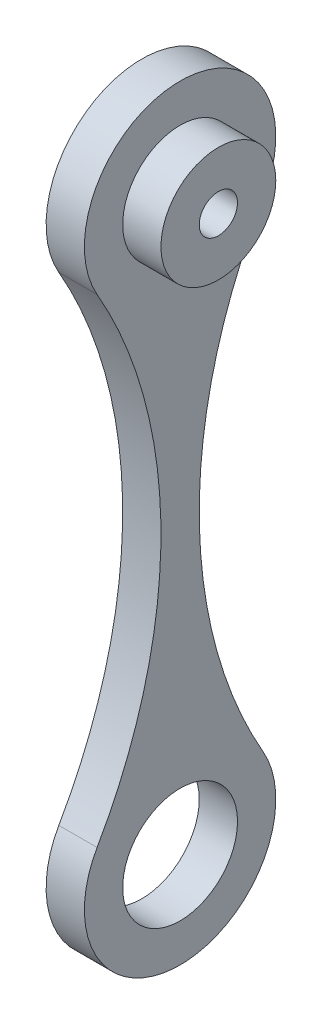
SolidWorks part; units mm, degrees
ref_plane "Front Plane" through (0, 0, 0) normal (0, 0, 1) x (1, 0, 0)
ref_plane "Top Plane" through (0, 0, 0) normal (0, 1, 0) x (1, 0, 0)
ref_plane "Right Plane" through (0, 0, 0) normal (1, 0, 0) x (0, 0, -1)
sketch "Sketch1" plane through (0, 0, 0) normal (1, 0, 0) x (0, 0, -1)
  line L0 (0, 0) -> (0, -150) construction
  circle A0 centre (0, 0) radius 25
  circle A1 centre (0, -150) radius 25
  circle A2 centre (0, 0) radius 15
  circle A3 centre (0, -150) radius 15
  arc A4 (-21.6805, -12.4481) -> (-21.6805, -137.5519) centre (-130.625, -75) cw
  arc A5 (21.6805, -12.4481) -> (21.6805, -137.5519) centre (130.625, -75) ccw
  point P15 (-5, -75)
  point P16 (5, -75)
  dimension "D1" = 50
  dimension "D2" = 50
  dimension "D5" = 10
  dimension "D6" = 10
  dimension "D3" = 150
  dimension "D4" = 10
extrude "Boss-Extrude1" add sketch "Sketch1" along normal blind 10 contours A2 A0 | L0 A0 A4 A1 | A0 L0 A1 A5 | A1 A3 | A2 region at (0, -21.0237, 12.1716) region at (0, -22.7345, -13.1621) region at (0, -75, 1.2697) region at (0, -128.9763, -12.1716)
sketch "Sketch2" plane through (10, 0, 0) normal (1, 0, 0) x (0, 0, -1)
  circle A0 centre (0, 0) radius 15
  arc A1 (21.6805, -12.4481) -> (-21.6805, -12.4481) centre (0, 0) ccw construction
  dimension "D1" = 10
extrude "Boss-Extrude2" add sketch "Sketch2" along normal blind 10
sketch "Sketch3" plane through (20, 0, 0) normal (1, 0, 0) x (0, 0, -1)
  circle A2 centre (0, 0) radius 5
  circle A3 centre (0, 0) radius 5
  dimension "D1" = 10
extrude "Cut-Extrude1" cut sketch "Sketch3" against normal blind 45
ref_plane "Plane1" through (15, 0, 0) normal (1, 0, 0) x (0, 0, -1)
ref_plane "Plane2" through (5, 0, 0) normal (1, 0, 0) x (0, 0, -1)
ref_axis "Axis1" through (0, 0, 0) along (1, 0, 0)
ref_axis "Axis2" through (10, -150, 0) along (-1, 0, 0)
ref_point "Point1"
ref_point "Point2"
